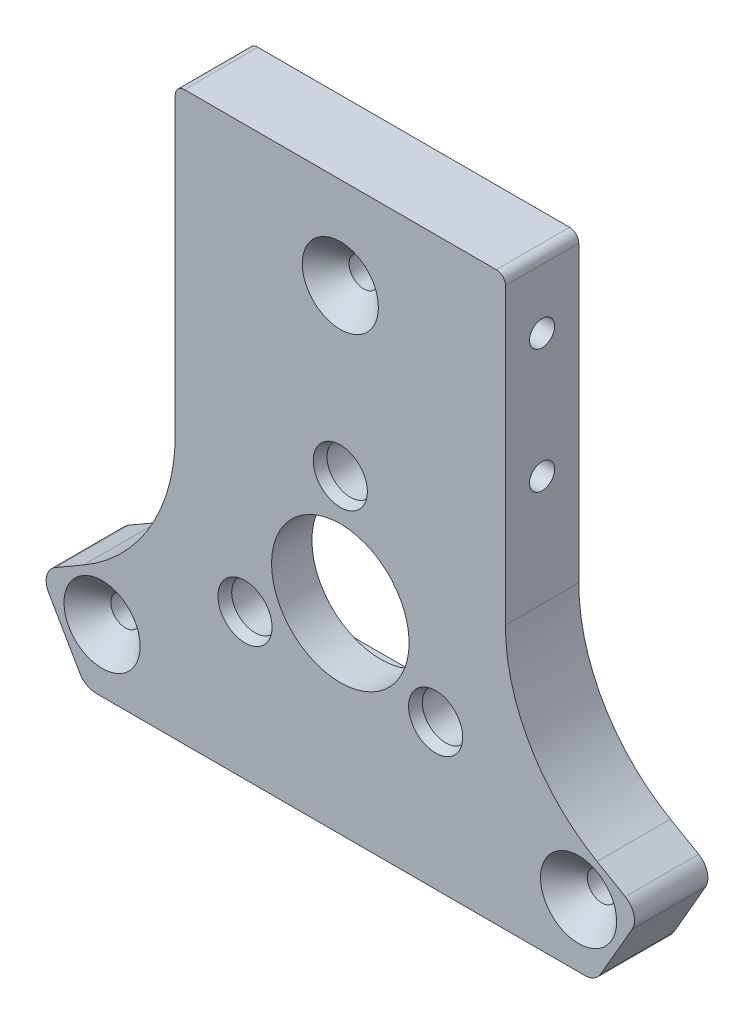
SolidWorks part; units mm, degrees
note: '?' marks a value the reader was unsure of.
other "tool plate" parameters "D3"=8, "D5"=17.4451, "D1"=15.1752, "D2"=4.8248, "D4"=5.0211
ref_plane "Front" through (0, 0, 0) normal (0, 0, 1) x (1, 0, 0)
ref_plane "Top" through (0, 0, 0) normal (0, 1, 0) x (1, 0, 0)
ref_plane "Right" through (0, 0, 0) normal (1, 0, 0) x (0, 0, -1)
sketch "Sketch1" plane through (0, 0, 0) normal (0, 0, 1) x (1, 0, 0)
  line L0 (0, 0) -> (0, 30) construction
  line L1 (0, 0) -> (-25.9808, -15) construction
  line L2 (0, 0) -> (25.9808, -15) construction
  line L4 (-6, -1) -> (6, -1)
  line L5 (-6, -1) -> (-6, 1)
  line L6 (-6, 1) -> (6, 1)
  line L7 (6, -1) -> (6, 1)
  line L8 (-6, -1) -> (6, 1) construction
  line L9 (-6, 1) -> (6, -1) construction
  circle A0 centre (0, 0) radius 2.5
  circle A1 centre (0, 30) radius 4
  circle A2 centre (25.9808, -15) radius 4
  circle A3 centre (-25.9808, -15) radius 4
  dimension "D4" = 5
  dimension "D7" = 8
  dimension "D1" = 30
  dimension "D2" = 120
  dimension "D3" = 120
  dimension "D5" = 12
  dimension "D6" = 2
ref_plane "Plane1" through (0, 30, 0) normal (0, 1, 0) x (1, 0, 0)
sketch "Sketch2" plane through (0, 0, 0) normal (0, 0, 1) x (1, 0, 0)
  line L0 (0, 0) -> (0, 30) construction
  line L1 (0, 0) -> (0, 30) construction
  line L2 (-18, 40) -> (18, 40)
  line L3 (18, 40) -> (18, -4.6188)
  line L4 (-18, 40) -> (-18, -4.6188)
  line L5 (18, -4.6188) -> (32.8109, -13.1699)
  line L6 (32.8109, -13.1699) -> (27.8109, -21.8301)
  line L7 (27.8109, -21.8301) -> (-27.8109, -21.8301)
  line L8 (0, 0) -> (25.9808, -15) construction
  line L9 (30.3109, -17.5) -> (25.9808, -15) construction
  line L10 (-32.8109, -13.1699) -> (-27.8109, -21.8301)
  line L11 (-18, -4.6188) -> (-32.8109, -13.1699)
  circle A0 centre (25.9808, -15) radius 4 construction
  circle A1 centre (0, 0) radius 7.5
  point P8 (0, 40)
  point P19 (0, -21.8301)
  dimension "D5" = 15
  dimension "D1" = 18
  dimension "D2" = 10
  dimension "D3" = 5
  dimension "D4" = 10
extrude "Boss-Extrude1" add sketch "Sketch2" along normal blind 8
hole_wizard "CSK for M3 Flat Head Machine Screw2" positions "Sketch8" profile "Sketch9" countersink size "M3" standard "ANSI Metric"
sketch "Sketch8" plane through (0, 0, 8) normal (0, 0, 1) x (1, 0, 0)
  point P0 (-25.9808, -15)
  point P3 (0, 30)
  point P6 (25.9808, -15)
sketch "Sketch9" plane through (-25.9808, -15, 8) normal (1, 0, 0) x (0, -1, 0)
  line L0 (0, 0) -> (0, 8.9604)
  line L1 (0, 8.9604) -> (1.6, 7.999)
  line L2 (1.6, 7.999) -> (1.6, 2.55)
  line L3 (1.6, 2.55) -> (4.15, 0)
  line L5 (4.15, 0) -> (0, 0)
  line L6 (-1.6, 2.55) -> (-4.15, 0) construction
  line L10 (0, 8.9604) -> (-1.6, 7.999) construction
  line L11 (0, -6.35) -> (0, 107.95) construction
  dimension "Hole Dia." = 3.2
  dimension "Hole Depth" = 7.999
  dimension "Near C'Sink Dia." = 8.3
  dimension "Near C'Sink Angle" = 90
  dimension "Drill Angle" = 118
fillet "Fillet1" radius 20 2 edges at (-18, -4.6188, 4) (18, -4.6188, 4)
sketch "Sketch44" plane through (0, 0, 0) normal (0, 0, -1) x (-1, 0, 0)
  line L0 (10.3923, 10) -> (-10.3923, 10)
  line L1 (0, -20) -> (17.3205, 10) construction
  line L2 (17.3205, 10) -> (-17.3205, 10) construction
  line L3 (-17.3205, 10) -> (0, -20) construction
  line L4 (-13.8564, 4) -> (-3.4641, -14)
  line L5 (3.4641, -14) -> (13.8564, 4)
  line L6 (-17.3205, 10) -> (0, -20) construction
  line L7 (0, -20) -> (17.3205, 10) construction
  line L8 (17.3205, 10) -> (-17.3205, 10) construction
  circle A0 centre (0, 0) radius 10 construction
  arc A1 (-3.4641, -14) -> (3.4641, -14) centre (0, -12) ccw
  arc A2 (10.3923, 10) -> (13.8564, 4) centre (10.3923, 6) cw
  arc A3 (-10.3923, 10) -> (-13.8564, 4) centre (-10.3923, 6) ccw
  dimension "D1" = 20
  dimension "D3" = 4
  dimension "D2" = 0
extrude "v-groove cutout" [suppressed] cut sketch "Sketch44" against normal blind 3.6
sketch "Sketch13" [suppressed] plane through (0, 0, 0) normal (0, 0, -1) x (-1, 0, 0)
  circle A0 centre (-10.3923, 6) radius 2.55
  circle A1 centre (10.3923, 6) radius 2.55
  circle A2 centre (0, -12) radius 2.55
  arc A3 (-10.3923, 10) -> (-13.8564, 4) centre (-10.3923, 6) ccw construction
  arc A4 (13.8564, 4) -> (10.3923, 10) centre (10.3923, 6) ccw construction
  arc A5 (-3.4641, -14) -> (3.4641, -14) centre (0, -12) ccw construction
  dimension "D1" = 5.1
extrude "standard tapered insert cutout" [suppressed] cut sketch "Sketch13" against normal through all and the other way through all
chamfer "taper for inserts" [suppressed] distance 0.4 angle 70
other "Move Face1" [suppressed] parameters "D1"=0.5
sketch "Sketch47" plane through (0, 0, 0) normal (0, 0, -1) x (-1, 0, 0)
  line L1 (-3.4641, 14) -> (-13.8564, -4)
  line L2 (-10.3923, -10) -> (10.3923, -10)
  line L3 (13.8564, -4) -> (3.4641, 14)
  circle A0 centre (0, 0) radius 10 construction
  arc A1 (10.3923, -10) -> (13.8564, -4) centre (10.3923, -6) ccw
  arc A2 (-13.8564, -4) -> (-10.3923, -10) centre (-10.3923, -6) ccw
  arc A3 (-3.4641, 14) -> (3.4641, 14) centre (0, 12) cw
  dimension "D1" = 20
  dimension "D2" = 4
extrude "v-groove cutout flipped" cut sketch "Sketch47" against normal blind 3.6
sketch "Sketch49" plane through (0, 0, 3.6) normal (0, 0, -1) x (-1, 0, 0)
  circle A0 centre (0, 12) radius 2.55
  circle A1 centre (10.3923, -6) radius 2.55
  circle A2 centre (-10.3923, -6) radius 2.55
  dimension "D1" = 5.1
extrude "Cut-Extrude3" cut sketch "Sketch49" against normal through all
chamfer "Chamfer2" distance 0.4 angle 70 3 edges at (7.8423, -6, 8) (-12.9423, -6, 8) (-2.55, 12, 8) first distance on face at (-2.55, 12, 8)
other "Move Face2" flip direction yes face at (-12.9904, -7.5, 1.8) face at (0, -10, 1.8) face at (12.9904, -7.5, 1.8) face at (8.6603, 5, 1.8) face at (0, 15, 1.8) face at (-8.6603, 5, 1.8) parameters "D1"=0.5
ref_axis "Axis2" through (0, 30, 0) along (0, 0, 1)?
sketch "Sketch46" plane through (0, 30, 0) normal (0, 1, 0) x (1, 0, 0)
  line L0 (0, 0) -> (0, 0.3) construction
  line L1 (0, 4.3) -> (0, -3.7)
  circle A0 centre (0, 0.3) radius 4 construction
  arc A1 (0, -3.7) -> (0, 4.3) centre (0, 0.3) cw
  dimension "D1" = 8
  dimension "D2" = 0.3
revolve "tool ball cutout" cut sketch "Sketch46" angle 360 about L0
pattern_circular "CirPattern2" count 3 over 360 about axis through (0, 0, 0) along (0, 0, 1) of "tool ball cutout"
sketch "Sketch20" plane through (18, 0, 0) normal (1, 0, 0) x (0, 0, -1)
  line L0 (-4, 32.5) -> (-4, 40) construction
  line L1 (-8, 40) -> (0, 40) construction
  line L2 (-4, 32.5) -> (-4, 19) construction
  circle A0 centre (-4, 19) radius 1.375
  circle A1 centre (-4, 32.5) radius 1.375
  dimension "D1" = 2.75
  dimension "D2" = 7.5
  dimension "D3" = 13.5
extrude "Tool Wing Screw Holes" cut sketch "Sketch20" against normal blind 4
mirror "Mirror2" about plane through (0, 0, 0) normal (1, 0, 0) of "Tool Wing Screw Holes"
ref_plane "Plane6" through (0, -5.8301, 0) normal (0, -1, 0) x (-1, 0, 0)
fillet "Fillet17" radius 2 4 edges at (27.8109, -21.8301, 4) (32.8109, -13.1699, 4) (-27.8109, -21.8301, 4) (-32.8109, -13.1699, 4)
ref_plane "Plane7" through (0, -15.8301, 0) normal (0, -1, 0) x (-1, 0, 0)
fillet "Fillet18" radius 1 2 edges at (-18, 40, 4) (18, 40, 4)
equation "\"base_tool_plate_width\"= 36"
equation "\"D1@Sketch2\"=\"base_tool_plate_width\"/2"
